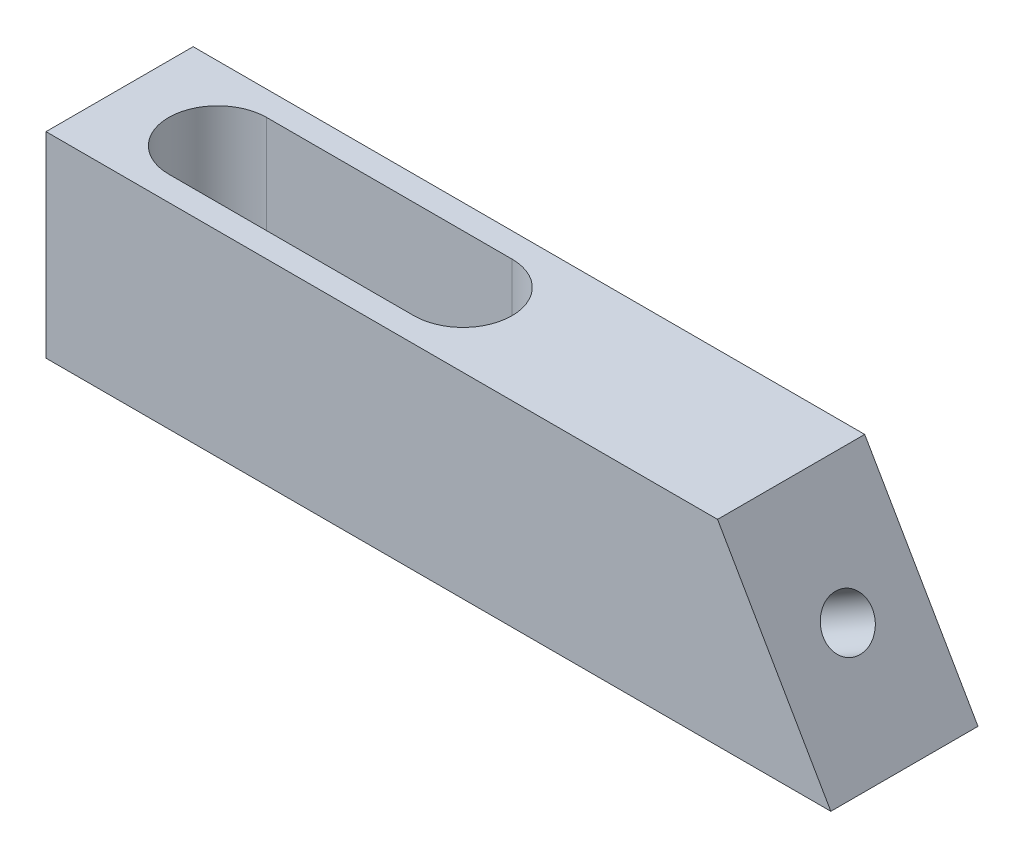
SolidWorks part; units mm, degrees
ref_plane "Front Plane" through (0, 0, 0) normal (0, 0, 1) x (1, 0, 0)
ref_plane "Top Plane" through (0, 0, 0) normal (0, 1, 0) x (1, 0, 0)
ref_plane "Right Plane" through (0, 0, 0) normal (1, 0, 0) x (0, 0, -1)
sketch "Sketch1" plane through (0, 0, 0) normal (0, 0, 1) x (1, 0, 0)
  line L0 (0, 0) -> (0, 25.4)
  line L1 (0, 25.4) -> (86.9353, 25.4)
  line L2 (86.9353, 25.4) -> (101.6, 0)
  line L3 (101.6, 0) -> (0, 0)
  point P3 (0, 0)
  point P7 (0, 0)
  dimension "D1" = 60
  dimension "D2" = 25.4
  dimension "D3" = 101.6
extrude "Boss-Extrude1" add sketch "Sketch1" along normal blind 19.05
ref_plane "Plane1" through (67.9511, 39.2316, 0) normal (0.866, 0.5, 0) x (0, 0, -1)
sketch "Sketch2" plane through (67.9511, 39.2316, 0) normal (0.866, 0.5, 0) x (0, 0, -1)
  line L0 (-9.525, -50.8) -> (-9.525, -24.6456) construction
  line L1 (-19.05, -50.8) -> (0, -50.8) construction
  line L2 (-15.875, -24.6456) -> (-3.175, -24.6456)
  line L3 (-3.175, -24.6456) -> (-3.175, -74.0762)
  line L4 (-3.175, -74.0762) -> (-15.875, -74.0762)
  line L5 (-15.875, -74.0762) -> (-15.875, -24.6456)
  line L6 (0, -50.8) -> (0, -21.4706) construction
  line L7 (-19.05, -21.4706) -> (0, -21.4706) construction
  point P6 (-9.525, -42.9951)
  point P9 (-9.525, -24.6456)
  point P10 (-9.525, -39.0136)
  dimension "D1" = 3.175
  dimension "D2" = 3.175
extrude "Cut-Extrude1" cut sketch "Sketch2" against normal through all
sketch "Sketch3" plane through (76.2, 43.9941, 0) normal (0.866, 0.5, 0) x (0, 0, -1)
  line L0 (-9.525, -36.1353) -> (-9.525, -50.8) construction
  line L1 (-19.05, -50.8) -> (0, -50.8) construction
  line L2 (0, -50.8) -> (0, -21.4706) construction
  circle A0 centre (-9.525, -36.1353) radius 3.1877
  point P7 (0, -36.1353)
  dimension "D1" = 6.3754
extrude "Cut-Extrude2" cut sketch "Sketch3" against normal through all
sketch "Sketch4" plane through (0, 25.4, 0) normal (0, 1, 0) x (1, 0, 0)
  line L0 (12.7, -9.525) -> (44.45, -9.525) construction
  line L1 (12.7, -3.175) -> (44.45, -3.175)
  line L2 (12.7, -15.875) -> (44.45, -15.875)
  line L3 (0, -19.05) -> (0, 0) construction
  line L4 (86.9353, 0) -> (0, 0) construction
  arc A0 (12.7, -3.175) -> (12.7, -15.875) centre (12.7, -9.525) ccw
  arc A1 (44.45, -15.875) -> (44.45, -3.175) centre (44.45, -9.525) ccw
  circle A2 centre (12.7, -9.525) radius 3.1877
  circle A3 centre (44.45, -9.525) radius 3.1877
  point P2 (28.575, -9.525)
  point P10 (0, -9.525)
  dimension "D4" = 6.3754
  dimension "D1" = 3.175
  dimension "D2" = 31.75
  dimension "D3" = 12.7
extrude "Cut-Extrude3" cut sketch "Sketch4" against normal blind 12.7 contours L1 A1 L2 A0
extrude "Cut-Extrude5" cut sketch "Sketch4<3>" against normal through all contours A2 | A3
sketch "Sketch4<3>" plane through (0, 25.4, 0) normal (0, 1, 0) x (1, 0, 0) same geometry as "Sketch4"
